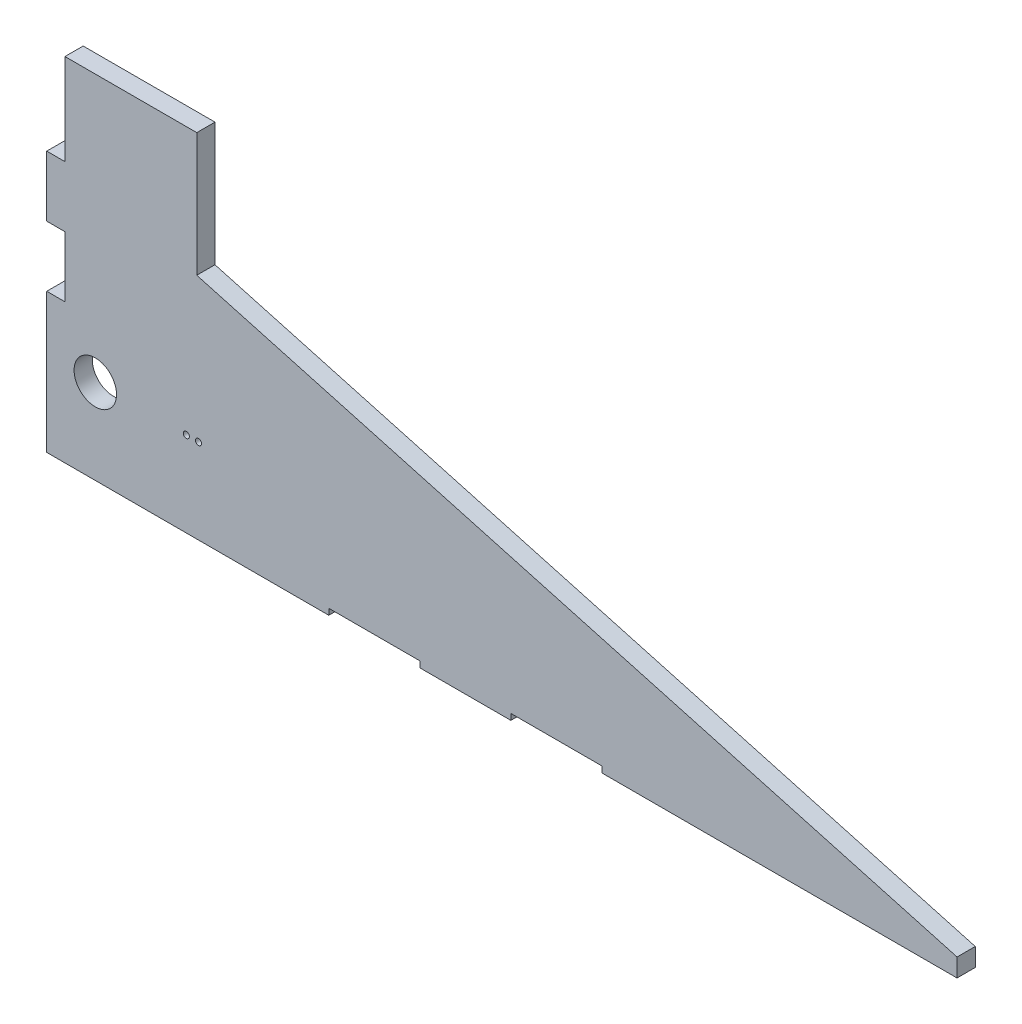
SolidWorks part; units mm, degrees
ref_plane "前视基准面" through (0, 0, 0) normal (0, 0, 1) x (1, 0, 0)
ref_plane "上视基准面" through (0, 0, 0) normal (0, 1, 0) x (1, 0, 0)
ref_plane "右视基准面" through (0, 0, 0) normal (1, 0, 0) x (0, 0, -1)
sketch "草图1" plane through (0, 0, 0) normal (0, 0, 1) x (1, 0, 0)
  line L0 (0, -1.0782) -> (0, -59.0782)
  line L1 (0, -59.0782) -> (150, -59.0782)
  line L3 (24.7207, -21.434) -> (24.7207, -1.0782)
  line L4 (24.7207, -1.0782) -> (0, -1.0782)
  line L5 (150, -59.0782) -> (150, -56.0782)
  line L6 (150, -56.0782) -> (24.7207, -21.434)
  dimension "D1" = 150
  dimension "D2" = 58
  dimension "D3" = 3
extrude "凸台-拉伸1" add sketch "草图1" along normal blind 0.5
sketch "草图2" plane through (0, 0, 0) normal (0, 0, -1) x (-1, 0, 0)
  line L0 (0, -1.0782) -> (-2.47, -1.0782)
  line L1 (-24.7207, -1.0782) -> (0, -1.0782) construction
  line L2 (-2.47, -1.0782) -> (-2.47, -54.0782)
  line L4 (-149.75, -59.0782) -> (0, -59.0782)
  line L5 (0, -59.0782) -> (0, -1.0782)
  line L6 (-150, -58.8282) -> (-150, -58.8207)
  line L7 (-149.7576, -58.5708) -> (-2.47, -54.0782)
  arc A0 (-150, -58.8207) -> (-149.7576, -58.5708) centre (-149.75, -58.8207) cw
  arc A1 (-150, -58.8282) -> (-149.75, -59.0782) centre (-149.75, -58.8282) ccw
  point P14 (-150, -58.5782)
  point P17 (-150, -59.0782)
  dimension "D3" = 0.25
  dimension "D1" = 5
  dimension "D2" = 0.5
extrude "凸台-拉伸2" add sketch "草图2" along normal blind 109.5
sketch "草图4" plane through (0, 0, 0.5) normal (0, 0, 1) x (1, 0, 0)
  line L0 (0, -59.0782) -> (150, -59.0782) construction
  line L1 (0, -1.0782) -> (0, -59.0782) construction
  circle A0 centre (6, -53.0782) radius 1
  dimension "D1" = 6
  dimension "D3" = 2
  dimension "D2" = 6
mirror "镜向3" about plane through (149.75, -58.8207, -109.5) normal (0, 0, 1) of bodies 102 106
sketch "草图8" plane through (-1.6457, -53.9527, 0) normal (0.0305, 0.9995, 0) x (0.9995, -0.0305, 0)
  line L0 (151.4737, 219) -> (151.4737, 0) construction
  line L1 (151.4737, 1) -> (91.4737, 1)
  line L2 (151.4737, 1) -> (151.4737, 9)
  line L3 (151.4737, 9) -> (91.4737, 9)
  line L4 (91.4737, 1) -> (91.4737, 9)
  line L5 (151.4737, 1) -> (91.4737, 9) construction
  line L6 (151.4737, 9) -> (91.4737, 1) construction
  line L7 (4.1176, 0) -> (151.4737, 0) construction
  line L8 (91.4737, 11) -> (151.4737, 11)
  line L9 (91.4737, 11) -> (91.4737, 19)
  line L10 (91.4737, 19) -> (151.4737, 19)
  line L11 (151.4737, 11) -> (151.4737, 19)
  line L12 (91.4737, 11) -> (151.4737, 19) construction
  line L13 (91.4737, 19) -> (151.4737, 11) construction
  line L14 (91.4737, 20.9474) -> (91.4737, 28.9474)
  line L15 (91.4737, 20.9474) -> (151.4737, 20.9474)
  line L16 (151.4737, 20.9474) -> (151.4737, 28.9474)
  line L17 (91.4737, 28.9474) -> (151.4737, 28.9474)
  line L18 (91.4737, 30.8947) -> (91.4737, 38.8947)
  line L19 (91.4737, 30.8947) -> (151.4737, 30.8947)
  line L20 (151.4737, 30.8947) -> (151.4737, 38.8947)
  line L21 (91.4737, 38.8947) -> (151.4737, 38.8947)
  line L22 (91.4737, 40.8421) -> (91.4737, 48.8421)
  line L23 (91.4737, 40.8421) -> (151.4737, 40.8421)
  line L24 (151.4737, 40.8421) -> (151.4737, 48.8421)
  line L25 (91.4737, 48.8421) -> (151.4737, 48.8421)
  line L26 (91.4737, 50.7895) -> (91.4737, 58.7895)
  line L27 (91.4737, 50.7895) -> (151.4737, 50.7895)
  line L28 (151.4737, 50.7895) -> (151.4737, 58.7895)
  line L29 (91.4737, 58.7895) -> (151.4737, 58.7895)
  line L30 (91.4737, 60.7368) -> (91.4737, 68.7368)
  line L31 (91.4737, 60.7368) -> (151.4737, 60.7368)
  line L32 (151.4737, 60.7368) -> (151.4737, 68.7368)
  line L33 (91.4737, 68.7368) -> (151.4737, 68.7368)
  line L34 (91.4737, 70.6842) -> (91.4737, 78.6842)
  line L35 (91.4737, 70.6842) -> (151.4737, 70.6842)
  line L36 (151.4737, 70.6842) -> (151.4737, 78.6842)
  line L37 (91.4737, 78.6842) -> (151.4737, 78.6842)
  line L38 (91.4737, 80.6316) -> (91.4737, 88.6316)
  line L39 (91.4737, 80.6316) -> (151.4737, 80.6316)
  line L40 (151.4737, 80.6316) -> (151.4737, 88.6316)
  line L41 (91.4737, 88.6316) -> (151.4737, 88.6316)
  line L42 (91.4737, 90.5789) -> (91.4737, 98.5789)
  line L43 (91.4737, 90.5789) -> (151.4737, 90.5789)
  line L44 (151.4737, 90.5789) -> (151.4737, 98.5789)
  line L45 (91.4737, 98.5789) -> (151.4737, 98.5789)
  line L46 (91.4737, 100.5263) -> (91.4737, 108.5263)
  line L47 (91.4737, 100.5263) -> (151.4737, 100.5263)
  line L48 (151.4737, 100.5263) -> (151.4737, 108.5263)
  line L49 (91.4737, 108.5263) -> (151.4737, 108.5263)
  line L50 (91.4737, 110.4737) -> (91.4737, 118.4737)
  line L51 (91.4737, 110.4737) -> (151.4737, 110.4737)
  line L52 (151.4737, 110.4737) -> (151.4737, 118.4737)
  line L53 (91.4737, 118.4737) -> (151.4737, 118.4737)
  line L54 (91.4737, 120.4211) -> (91.4737, 128.4211)
  line L55 (91.4737, 120.4211) -> (151.4737, 120.4211)
  line L56 (151.4737, 120.4211) -> (151.4737, 128.4211)
  line L57 (91.4737, 128.4211) -> (151.4737, 128.4211)
  line L58 (91.4737, 130.3684) -> (91.4737, 138.3684)
  line L59 (91.4737, 130.3684) -> (151.4737, 130.3684)
  line L60 (151.4737, 130.3684) -> (151.4737, 138.3684)
  line L61 (91.4737, 138.3684) -> (151.4737, 138.3684)
  line L62 (91.4737, 140.3158) -> (91.4737, 148.3158)
  line L63 (91.4737, 140.3158) -> (151.4737, 140.3158)
  line L64 (151.4737, 140.3158) -> (151.4737, 148.3158)
  line L65 (91.4737, 148.3158) -> (151.4737, 148.3158)
  line L66 (91.4737, 150.2632) -> (91.4737, 158.2632)
  line L67 (91.4737, 150.2632) -> (151.4737, 150.2632)
  line L68 (151.4737, 150.2632) -> (151.4737, 158.2632)
  line L69 (91.4737, 158.2632) -> (151.4737, 158.2632)
  line L70 (91.4737, 160.2105) -> (91.4737, 168.2105)
  line L71 (91.4737, 160.2105) -> (151.4737, 160.2105)
  line L72 (151.4737, 160.2105) -> (151.4737, 168.2105)
  line L73 (91.4737, 168.2105) -> (151.4737, 168.2105)
  line L74 (91.4737, 170.1579) -> (91.4737, 178.1579)
  line L75 (91.4737, 170.1579) -> (151.4737, 170.1579)
  line L76 (151.4737, 170.1579) -> (151.4737, 178.1579)
  line L77 (91.4737, 178.1579) -> (151.4737, 178.1579)
  line L78 (91.4737, 180.1053) -> (91.4737, 188.1053)
  line L79 (91.4737, 180.1053) -> (151.4737, 180.1053)
  line L80 (151.4737, 180.1053) -> (151.4737, 188.1053)
  line L81 (91.4737, 188.1053) -> (151.4737, 188.1053)
  line L82 (91.4737, 190.0526) -> (91.4737, 198.0526)
  line L83 (91.4737, 190.0526) -> (151.4737, 190.0526)
  line L84 (151.4737, 190.0526) -> (151.4737, 198.0526)
  line L85 (91.4737, 198.0526) -> (151.4737, 198.0526)
  line L86 (91.4737, 200) -> (91.4737, 208)
  line L87 (91.4737, 200) -> (151.4737, 200)
  line L88 (151.4737, 200) -> (151.4737, 208)
  line L89 (91.4737, 208) -> (151.4737, 208)
  line L90 (4.1176, 219) -> (151.4737, 219) construction
  line L91 (151.4737, 210) -> (91.4737, 210)
  line L92 (151.4737, 210) -> (151.4737, 218)
  line L93 (151.4737, 218) -> (91.4737, 218)
  line L94 (91.4737, 210) -> (91.4737, 218)
  line L95 (151.4737, 210) -> (91.4737, 218) construction
  line L96 (151.4737, 218) -> (91.4737, 210) construction
  point P4 (121.4737, 5)
  point P11 (121.4737, 15)
  point P94 (121.4737, 214)
  dimension "D1" = 60
  dimension "D2" = 8
  dimension "D3" = 8
  dimension "D4" = 2
  dimension "D5" = 1
  dimension "D7" = 8
  dimension "D8" = 2
  dimension "D9" = 60
  dimension "D10" = 1
  dimension "D6" = 20
extrude "切除-拉伸2" cut sketch "草图8" against normal blind 10
sketch "草图9" plane through (-1.6457, -53.9527, 0) normal (0.0305, 0.9995, 0) x (0.9995, -0.0305, 0)
  line L0 (151.64, 219) -> (153.0857, 219)
  line L1 (151.4737, 1) -> (151.7162, 1)
  line L2 (151.4737, 1) -> (151.4737, 219)
  line L3 (151.4737, 219) -> (151.64, 219)
  line L5 (153.0857, 219) -> (154.856, 1)
  line L6 (151.4737, 219) -> (151.7162, 1) construction
  line L7 (154.856, 1) -> (151.7162, 1)
  point P4 (151.5944, 110.4978)
extrude "切除-拉伸3" cut sketch "草图9" against normal blind 10
extrude "凸台-拉伸4" add sketch "草图1<3>" against normal blind 2.5
sketch "草图1<3>" plane through (0, 0, 0) normal (0, 0, 1) x (1, 0, 0) same geometry as "草图1"
fillet "圆角3" radius 0.25 22 edges at (149.7576, -58.5708, -179.1316) (149.7576, -58.5708, -189.0789) (149.7576, -58.5708, -199.0263) (149.7576, -58.5708, -209) (149.7576, -58.5708, -218.5) (149.7576, -58.5708, -89.6053) (149.7576, -58.5708, -99.5526) (149.7576, -58.5708, -109.5) (149.7576, -58.5708, -119.4474) (149.7576, -58.5708, -129.3947) (149.7576, -58.5708, -139.3421) (149.7576, -58.5708, -149.2895) (149.7576, -58.5708, -159.2368) (149.7576, -58.5708, -169.1842) (149.7576, -58.5708, -79.6579) (149.7576, -58.5708, -69.7105) (149.7576, -58.5708, -59.7632) (149.7576, -58.5708, -49.8158) (149.7576, -58.5708, -39.8684) (149.7576, -58.5708, -29.9211) (149.7576, -58.5708, -19.9737) (149.7576, -58.5708, -10)
fillet "圆角4" radius 0.25 22 edges at (149.7421, -59.0782, -49.8158) (149.7421, -59.0782, -39.8684) (149.7421, -59.0782, -29.9211) (149.7421, -59.0782, -19.9737) (149.7421, -59.0782, -10) (149.7421, -59.0782, -69.7105) (149.7421, -59.0782, -59.7632) (149.7421, -59.0782, -89.6053) (149.7421, -59.0782, -79.6579) (149.7421, -59.0782, -129.3947) (149.7421, -59.0782, -119.4474) (149.7421, -59.0782, -109.5) (149.7421, -59.0782, -99.5526) (149.7421, -59.0782, -139.3421) (149.7421, -59.0782, -149.2895) (149.7421, -59.0782, -159.2368) (149.7421, -59.0782, -169.1842) (149.7421, -59.0782, -218.5) (149.7421, -59.0782, -209) (149.7421, -59.0782, -199.0263) (149.7421, -59.0782, -189.0789) (149.7421, -59.0782, -179.1316)
ref_plane "基准面1" through (0, 0, -109.5) normal (0, 0, 1) x (1, 0, 0)
mirror "镜向4" about plane through (0, 0, -109.5) normal (0, 0, 1) of "凸台-拉伸4"
sketch "草图7" plane through (0, 0, 0.5) normal (0, 0, 1) x (1, 0, 0)
  line L0 (0, -1.0782) -> (0, -59.0782) construction
  line L1 (8, -45.0782) -> (23, -45.0782) construction
  line L2 (0, -59.0782) -> (150, -59.0782) construction
  line L3 (23, -45.0782) -> (25, -45.0782) construction
  circle A0 centre (8, -45.0782) radius 3.5
  circle A1 centre (25, -45.0782) radius 0.5
  circle A2 centre (23, -45.0782) radius 0.5
  dimension "D1" = 8
  dimension "D3" = 17
  dimension "D4" = 2
  dimension "D2" = 14
extrude "切除-拉伸4" cut sketch "草图7" against normal blind 244
sketch "草图11" plane through (150, 0, 0) normal (1, 0, 0) x (0, 0, -1)
  line L1 (2.5, -59.0782) -> (309.3124, -59.0782)
  line L2 (2.5, -59.0782) -> (2.5, 76.7688)
  line L3 (2.5, 76.7688) -> (309.3124, 76.7688)
  line L4 (309.3124, -59.0782) -> (309.3124, 76.7688)
  line L5 (2.5, -59.0782) -> (309.3124, 76.7688) construction
  line L6 (2.5, 76.7688) -> (309.3124, -59.0782) construction
  point P4 (155.9062, 8.8453)
extrude "切除-拉伸6" cut sketch "草图11" against normal blind 266
sketch "草图12" plane through (0, 0, 0.5) normal (0, 0, 1) x (1, 0, 0)
  line L0 (0, -63.0782) -> (0, -5.0782) construction
  line L1 (0, -5.0782) -> (155.5397, -5.0782) construction
  circle A0 centre (1, -9.0782) radius 0.5
  circle A1 centre (1, -14.0782) radius 0.5
  dimension "D1" = 1
  dimension "D2" = 1
  dimension "D3" = 5
  dimension "D4" = 4
sketch "草图15" plane through (0, 0, 0) normal (-1, 0, 0) x (0, 0, 1)
  line L0 (-2.5, -1.0782) -> (-2.5, -59.0782) construction
  line L1 (0.5, -1.0782) -> (-2.5, -1.0782)
  line L2 (0.5, -1.0782) -> (0.5, -16.0782)
  line L3 (0.5, -16.0782) -> (-2.5, -16.0782)
  line L4 (-2.5, -1.0782) -> (-2.5, -16.0782)
  line L5 (0.5, -1.0782) -> (-2.5, -16.0782) construction
  line L6 (0.5, -16.0782) -> (-2.5, -1.0782) construction
  line L7 (0.5, -1.0782) -> (0.5, -59.0782) construction
  line L8 (-2.5, -26.0782) -> (0.5, -26.0782)
  line L9 (-2.5, -26.0782) -> (-2.5, -36.0782)
  line L10 (-2.5, -36.0782) -> (0.5, -36.0782)
  line L11 (0.5, -26.0782) -> (0.5, -36.0782)
  line L12 (-2.5, -26.0782) -> (0.5, -36.0782) construction
  line L13 (-2.5, -36.0782) -> (0.5, -26.0782) construction
  point P5 (-1, -8.5782)
  point P12 (-1, -31.0782)
  point P15 (-1, -26.0782)
  dimension "D1" = 15
  dimension "D2" = 10
  dimension "D3" = 10
extrude "切除-拉伸9" cut sketch "草图15" against normal blind 3
sketch "草图16" plane through (0, -59.0782, 0) normal (0, -1, 0) x (-1, 0, 0)
  line L0 (0, 2.5) -> (-150, 2.5) construction
  line L1 (-91.4737, 2.5) -> (-76.4737, 2.5)
  line L2 (-91.4737, 2.5) -> (-91.4737, -0.5)
  line L3 (-91.4737, -0.5) -> (-76.4737, -0.5)
  line L4 (-76.4737, 2.5) -> (-76.4737, -0.5)
  line L5 (-91.4737, 2.5) -> (-76.4737, -0.5) construction
  line L6 (-91.4737, -0.5) -> (-76.4737, 2.5) construction
  line L7 (0, -0.5) -> (-150, -0.5) construction
  line L9 (-61.4737, -0.5) -> (-46.4737, -0.5)
  line L10 (-61.4737, -0.5) -> (-61.4737, 2.5)
  line L11 (-61.4737, 2.5) -> (-46.4737, 2.5)
  line L12 (-46.4737, -0.5) -> (-46.4737, 2.5)
  line L13 (-61.4737, -0.5) -> (-46.4737, 2.5) construction
  line L14 (-61.4737, 2.5) -> (-46.4737, -0.5) construction
  point P4 (-83.9737, 1)
  point P13 (-53.9737, 1)
  dimension "D1" = 15
  dimension "D2" = 15
  dimension "D3" = 15
extrude "切除-拉伸10" cut sketch "草图16" against normal blind 1 contours L1 L4 L3 L2 | L9 L12 L11 L10
sketch "草图17" plane through (0, 0, -2.5) normal (0, 0, -1) x (-1, 0, 0)
  line L0 (-150, -56.0782) -> (-100.3503, -42.3483)
  line L1 (-150, -59.0782) -> (-150, -56.0782) construction
  line L2 (-150, -56.0782) -> (-24.7207, -21.434) construction
  line L3 (-100.3503, -42.3483) -> (-52.6063, -29.1454)
  line L4 (-52.6063, -29.1454) -> (-52.6063, -58.0782)
  line L5 (-52.6063, -58.0782) -> (-61.4737, -58.0782)
  line L6 (-61.4737, -58.0782) -> (-61.4737, -59.0782) construction
  line L7 (-61.4737, -58.0782) -> (-46.4737, -58.0782) construction
  line L8 (-61.4737, -58.0782) -> (-61.4737, -59.0782)
  line L9 (-61.4737, -59.0782) -> (-76.4737, -59.0782) construction
  line L10 (-61.4737, -59.0782) -> (-76.4737, -59.0782)
  line L11 (-76.4737, -59.0782) -> (-76.4737, -58.0782)
  line L12 (-76.4737, -58.0782) -> (-76.4737, -59.0782) construction
  line L13 (-76.4737, -58.0782) -> (-91.4737, -58.0782)
  line L14 (-91.4737, -58.0782) -> (-76.4737, -58.0782) construction
  line L15 (-91.4737, -58.0782) -> (-91.4737, -59.0782)
  line L16 (-91.4737, -59.0782) -> (-150, -59.0782) construction
  line L17 (-91.4737, -59.0782) -> (-150, -59.0782)
  line L18 (-150, -59.0782) -> (-150, -56.0782)
